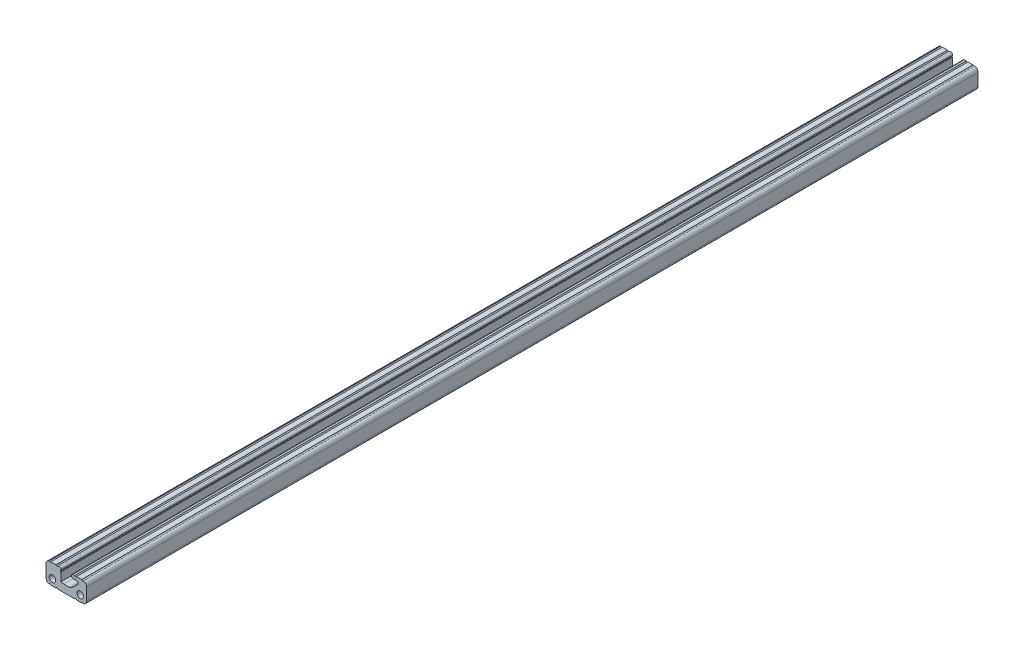
SolidWorks part; units mm, degrees
ref_plane "Front Plane" through (0, 0, 0) normal (0, 0, 1) x (1, 0, 0)
ref_plane "Top Plane" through (0, 0, 0) normal (0, 1, 0) x (1, 0, 0)
ref_plane "Right Plane" through (0, 0, 0) normal (1, 0, 0) x (0, 0, -1)
sketch "Sketch1" plane through (0, 0, 0) normal (0, 0, 1) x (1, 0, 0)
  line L0 (0, 6.35) -> (0, -6.35) construction
  line L1 (0, -6.35) -> (12.7, -6.35)
  line L2 (12.7, -6.35) -> (12.7, 6.35)
  line L3 (12.7, 6.35) -> (3.2512, 6.35)
  line L4 (3.2512, 6.35) -> (3.2512, 4.1402)
  line L5 (3.2512, 4.1402) -> (6.4224, 4.1402)
  line L6 (7.1255, 2.4426) -> (2.9811, -1.7018)
  line L7 (2.9811, -1.7018) -> (0, -1.7018)
  circle A0 centre (8.7249, -2.3876) radius 2.032
  arc A1 (6.4224, 4.1402) -> (7.1255, 2.4426) centre (6.4224, 3.1458) cw
  dimension "Center Hole Diameter" = 4.064
  dimension "D3" = 0.9944
  dimension "Rail Height" = 25.4
  dimension "Rail Width" = 12.7
  dimension "Hole CtoC" = 17.4498
  dimension "D1" = 3.9624
  dimension "T-Slot Width" = 6.5024
  dimension "Thickness" = 2.2098
  dimension "Inner Slot Width" = 14.8336
  dimension "Slot Depth" = 5.842
  dimension "D2" = 45
sketch "Sketch2" plane through (0, 0, 0) normal (1, 0, 0) x (0, 0, -1)
  line L0 (-304.8, -6.35) -> (304.8, -6.35) construction
  line L1 (-279.4, 0) -> (279.4, 0) construction
  dimension "Length" = 609.6
sketch "Sketch3" plane through (0, 0, 0) normal (0, 0, 1) x (1, 0, 0)
  line L0 (3.2512, 6.35) -> (3.2512, 4.1402) construction
  line L1 (12.7, 6.35) -> (3.2512, 6.35) construction
  line L2 (3.2512, 4.1402) -> (6.4224, 4.1402) construction
  line L3 (3.2512, 5.3556) -> (3.2512, 5.1346)
  line L4 (12.7, -6.35) -> (12.7, 6.35) construction
  line L5 (0, -6.35) -> (12.7, -6.35) construction
  line L6 (2.9811, -1.7018) -> (0, -1.7018) construction
  line L7 (7.1255, 2.4426) -> (2.9811, -1.7018) construction
  line L8 (0, -1.7018) -> (1.7454, -1.7018)
  line L9 (4.2456, 4.1402) -> (6.4224, 4.1402)
  line L10 (3.8549, -0.828) -> (7.1255, 2.4426)
  line L11 (0, -1.7018) -> (0, -6.35)
  line L12 (0, -6.35) -> (10.16, -6.35)
  line L13 (12.7, -3.81) -> (12.7, 3.81)
  line L14 (4.2456, 6.35) -> (10.16, 6.35)
  arc A0 (3.2512, 5.3556) -> (4.2456, 6.35) centre (4.2456, 5.3556) cw
  arc A1 (3.2512, 5.1346) -> (4.2456, 4.1402) centre (4.2456, 5.1346) ccw
  arc A2 (7.1255, 2.4426) -> (6.4224, 4.1402) centre (6.4224, 3.1458) ccw construction
  arc A3 (10.16, 6.35) -> (12.7, 3.81) centre (10.16, 3.81) cw
  arc A4 (10.16, -6.35) -> (12.7, -3.81) centre (10.16, -3.81) ccw
  arc A5 (7.1255, 2.4426) -> (6.4224, 4.1402) centre (6.4224, 3.1458) ccw
  circle A6 centre (8.7249, -2.3876) radius 2.032 construction
  circle A7 centre (8.7249, -2.3876) radius 2.032
  arc A8 (1.7454, -1.7018) -> (3.8549, -0.828) centre (1.7454, 1.2814) ccw
  dimension "D2" = 2.9832
extrude "Boss-Extrude1" add sketch "Sketch3" along normal mid plane 609.6
sketch "Sketch4" plane through (0, 0, 0) normal (0, 0, 1) x (1, 0, 0)
  line L0 (12.7, 6.35) -> (3.2512, 6.35) construction
  line L1 (0, -6.35) -> (12.7, -6.35) construction
  line L2 (10.7569, -2.3876) -> (10.7569, 6.35) construction
  line L3 (6.4224, 3.1458) -> (6.4224, 6.35) construction
  circle A0 centre (5.8699, 6.35) radius 0.5524
  circle A1 centre (10.2045, 6.35) radius 0.5524
  circle A2 centre (5.8699, -6.35) radius 0.5524
  circle A3 centre (10.2045, -6.35) radius 0.5524
  circle A4 centre (8.7249, -2.3876) radius 2.032 construction
  dimension "D1" = 1.1049
extrude "Cut-Extrude1" cut sketch "Sketch4" against normal through all both and the other way through all
mirror "Mirror1" about plane through (0, 0, 0) normal (1, 0, 0) of bodies 135
sketch "Sketch5" plane through (0, 0, 304.8) normal (0, 0, 1) x (1, 0, 0)
  line L16 (9.652, 6.35) -> (6.4224, 6.35)
  line L17 (5.3175, 6.35) -> (4.2456, 6.35)
  line L18 (3.2512, 5.3556) -> (3.2512, 5.1346)
  line L19 (4.2456, 4.1402) -> (6.4224, 4.1402)
  line L20 (7.1255, 2.4426) -> (3.8549, -0.828)
  line L21 (1.7454, -1.7018) -> (-1.7454, -1.7018)
  line L22 (-3.8549, -0.828) -> (-7.1255, 2.4426)
  line L23 (-6.4224, 4.1402) -> (-4.2456, 4.1402)
  line L24 (-3.2512, 5.1346) -> (-3.2512, 5.3556)
  line L25 (-4.2456, 6.35) -> (-5.3175, 6.35)
  line L26 (-6.4224, 6.35) -> (-9.652, 6.35)
  line L27 (-12.7, 3.81) -> (-12.7, -3.81)
  line L28 (-9.652, -6.35) -> (-6.4224, -6.35)
  line L29 (-5.3175, -6.35) -> (5.3175, -6.35)
  line L30 (6.4224, -6.35) -> (9.652, -6.35)
  line L31 (12.7, -3.81) -> (12.7, 3.81)
  line L32 (9.652, 6.35) -> (6.4224, 6.35)
  line L33 (5.3175, 6.35) -> (4.2456, 6.35)
  line L34 (3.2512, 5.3556) -> (3.2512, 5.1346)
  line L35 (4.2456, 4.1402) -> (6.4224, 4.1402)
  line L36 (7.1255, 2.4426) -> (3.8549, -0.828)
  line L37 (1.7454, -1.7018) -> (-1.7454, -1.7018)
  line L38 (-3.8549, -0.828) -> (-7.1255, 2.4426)
  line L39 (-6.4224, 4.1402) -> (-4.2456, 4.1402)
  line L40 (-3.2512, 5.1346) -> (-3.2512, 5.3556)
  line L41 (-4.2456, 6.35) -> (-5.3175, 6.35)
  line L42 (-6.4224, 6.35) -> (-9.652, 6.35)
  line L43 (-12.7, 3.81) -> (-12.7, -3.81)
  line L44 (-9.652, -6.35) -> (-6.4224, -6.35)
  line L45 (-5.3175, -6.35) -> (5.3175, -6.35)
  line L46 (6.4224, -6.35) -> (9.652, -6.35)
  line L47 (12.7, -3.81) -> (12.7, 3.81)
  arc A20 (12.7, 3.81) -> (10.7524, 6.2799) centre (10.16, 3.81) ccw
  arc A21 (9.652, 6.35) -> (10.7524, 6.2799) centre (10.2045, 6.35) ccw
  arc A22 (5.3175, 6.35) -> (6.4224, 6.35) centre (5.8699, 6.35) ccw
  arc A23 (4.2456, 6.35) -> (3.2512, 5.3556) centre (4.2456, 5.3556) ccw
  arc A24 (3.2512, 5.1346) -> (4.2456, 4.1402) centre (4.2456, 5.1346) ccw
  arc A25 (7.1255, 2.4426) -> (6.4224, 4.1402) centre (6.4224, 3.1458) ccw
  arc A26 (1.7454, -1.7018) -> (3.8549, -0.828) centre (1.7454, 1.2814) ccw
  arc A27 (-3.8549, -0.828) -> (-1.7454, -1.7018) centre (-1.7454, 1.2814) ccw
  arc A28 (-6.4224, 4.1402) -> (-7.1255, 2.4426) centre (-6.4224, 3.1458) ccw
  arc A29 (-4.2456, 4.1402) -> (-3.2512, 5.1346) centre (-4.2456, 5.1346) ccw
  arc A30 (-3.2512, 5.3556) -> (-4.2456, 6.35) centre (-4.2456, 5.3556) ccw
  arc A31 (-6.4224, 6.35) -> (-5.3175, 6.35) centre (-5.8699, 6.35) ccw
  arc A32 (-10.7524, 6.2799) -> (-9.652, 6.35) centre (-10.2045, 6.35) ccw
  arc A33 (-10.7524, 6.2799) -> (-12.7, 3.81) centre (-10.16, 3.81) ccw
  arc A34 (-12.7, -3.81) -> (-10.7524, -6.2799) centre (-10.16, -3.81) ccw
  arc A35 (-9.652, -6.35) -> (-10.7524, -6.2799) centre (-10.2045, -6.35) ccw
  arc A36 (-5.3175, -6.35) -> (-6.4224, -6.35) centre (-5.8699, -6.35) ccw
  arc A37 (6.4224, -6.35) -> (5.3175, -6.35) centre (5.8699, -6.35) ccw
  arc A38 (10.7524, -6.2799) -> (9.652, -6.35) centre (10.2045, -6.35) ccw
  arc A39 (10.7524, -6.2799) -> (12.7, -3.81) centre (10.16, -3.81) ccw
  arc A40 (12.7, 3.81) -> (10.7524, 6.2799) centre (10.16, 3.81) ccw
  arc A41 (9.652, 6.35) -> (10.7524, 6.2799) centre (10.2045, 6.35) ccw
  arc A42 (5.3175, 6.35) -> (6.4224, 6.35) centre (5.8699, 6.35) ccw
  arc A43 (4.2456, 6.35) -> (3.2512, 5.3556) centre (4.2456, 5.3556) ccw
  arc A44 (3.2512, 5.1346) -> (4.2456, 4.1402) centre (4.2456, 5.1346) ccw
  arc A45 (7.1255, 2.4426) -> (6.4224, 4.1402) centre (6.4224, 3.1458) ccw
  arc A46 (1.7454, -1.7018) -> (3.8549, -0.828) centre (1.7454, 1.2814) ccw
  arc A47 (-3.8549, -0.828) -> (-1.7454, -1.7018) centre (-1.7454, 1.2814) ccw
  arc A48 (-6.4224, 4.1402) -> (-7.1255, 2.4426) centre (-6.4224, 3.1458) ccw
  arc A49 (-4.2456, 4.1402) -> (-3.2512, 5.1346) centre (-4.2456, 5.1346) ccw
  arc A50 (-3.2512, 5.3556) -> (-4.2456, 6.35) centre (-4.2456, 5.3556) ccw
  arc A51 (-6.4224, 6.35) -> (-5.3175, 6.35) centre (-5.8699, 6.35) ccw
  arc A52 (-10.7524, 6.2799) -> (-9.652, 6.35) centre (-10.2045, 6.35) ccw
  arc A53 (-10.7524, 6.2799) -> (-12.7, 3.81) centre (-10.16, 3.81) ccw
  arc A54 (-12.7, -3.81) -> (-10.7524, -6.2799) centre (-10.16, -3.81) ccw
  arc A55 (-9.652, -6.35) -> (-10.7524, -6.2799) centre (-10.2045, -6.35) ccw
  arc A56 (-5.3175, -6.35) -> (-6.4224, -6.35) centre (-5.8699, -6.35) ccw
  arc A57 (6.4224, -6.35) -> (5.3175, -6.35) centre (5.8699, -6.35) ccw
  arc A58 (10.7524, -6.2799) -> (9.652, -6.35) centre (10.2045, -6.35) ccw
  arc A59 (10.7524, -6.2799) -> (12.7, -3.81) centre (10.16, -3.81) ccw
  dimension "D1" = 0
extrude "Cut-Extrude2" cut sketch "Sketch5" against normal offset from surface (50.8 mm away) 558.8 up to face at (0, 1.3921, -304.8)
sketch "Sketch6" plane through (0, 0, -304.8) normal (0, 0, -1) x (-1, 0, 0)
  line L0 (-4.2456, 4.1402) -> (-3.2512, 4.1402) construction
  line L1 (-3.2512, 4.1402) -> (-3.2512, -1.2939) construction
  line L2 (0, 6.985) -> (0, -6.985) construction
  line L3 (6.4224, 4.1402) -> (4.2456, 4.1402)
  line L4 (3.8549, -0.828) -> (7.1255, 2.4426)
  line L5 (3.2512, 4.1402) -> (3.2512, -1.2939)
  line L6 (4.2456, 4.1402) -> (3.2512, 4.1402)
  line L16 (-12.7, 3.81) -> (-12.7, -3.81)
  line L17 (-9.652, -6.35) -> (-6.4224, -6.35)
  line L18 (-5.3175, -6.35) -> (5.3175, -6.35)
  line L19 (6.4224, -6.35) -> (9.652, -6.35)
  line L20 (12.7, -3.81) -> (12.7, 3.81)
  line L21 (9.652, 6.35) -> (6.4224, 6.35)
  line L22 (5.3175, 6.35) -> (4.2456, 6.35)
  line L23 (3.2512, 5.3556) -> (3.2512, 5.1346)
  line L24 (4.2456, 4.1402) -> (6.4224, 4.1402)
  line L25 (7.1255, 2.4426) -> (3.8549, -0.828)
  line L26 (1.7454, -1.7018) -> (-1.7454, -1.7018)
  line L27 (-3.8549, -0.828) -> (-7.1255, 2.4426)
  line L28 (-6.4224, 4.1402) -> (-4.2456, 4.1402)
  line L29 (-3.2512, 5.1346) -> (-3.2512, 5.3556)
  line L30 (-4.2456, 6.35) -> (-5.3175, 6.35)
  line L31 (-6.4224, 6.35) -> (-9.652, 6.35)
  line L43 (-3.8549, -0.828) -> (-7.1255, 2.4426) construction
  line L44 (-6.4224, 4.1402) -> (-4.2456, 4.1402) construction
  arc A0 (6.4224, 4.1402) -> (7.1255, 2.4426) centre (6.4224, 3.1458) cw
  arc A1 (3.8549, -0.828) -> (3.2512, -1.2939) centre (1.7454, 1.2814) cw
  arc A20 (-10.7524, 6.2799) -> (-9.652, 6.35) centre (-10.2045, 6.35) ccw
  arc A21 (-10.7524, 6.2799) -> (-12.7, 3.81) centre (-10.16, 3.81) ccw
  arc A22 (-12.7, -3.81) -> (-10.7524, -6.2799) centre (-10.16, -3.81) ccw
  arc A23 (-9.652, -6.35) -> (-10.7524, -6.2799) centre (-10.2045, -6.35) ccw
  arc A24 (-5.3175, -6.35) -> (-6.4224, -6.35) centre (-5.8699, -6.35) ccw
  arc A25 (6.4224, -6.35) -> (5.3175, -6.35) centre (5.8699, -6.35) ccw
  arc A26 (10.7524, -6.2799) -> (9.652, -6.35) centre (10.2045, -6.35) ccw
  arc A27 (10.7524, -6.2799) -> (12.7, -3.81) centre (10.16, -3.81) ccw
  arc A28 (12.7, 3.81) -> (10.7524, 6.2799) centre (10.16, 3.81) ccw
  arc A29 (9.652, 6.35) -> (10.7524, 6.2799) centre (10.2045, 6.35) ccw
  arc A30 (5.3175, 6.35) -> (6.4224, 6.35) centre (5.8699, 6.35) ccw
  arc A31 (4.2456, 6.35) -> (3.2512, 5.3556) centre (4.2456, 5.3556) ccw
  arc A32 (3.2512, 5.1346) -> (4.2456, 4.1402) centre (4.2456, 5.1346) ccw
  arc A33 (7.1255, 2.4426) -> (6.4224, 4.1402) centre (6.4224, 3.1458) ccw
  arc A34 (1.7454, -1.7018) -> (3.8549, -0.828) centre (1.7454, 1.2814) ccw
  arc A35 (-3.8549, -0.828) -> (-1.7454, -1.7018) centre (-1.7454, 1.2814) ccw
  arc A36 (-6.4224, 4.1402) -> (-7.1255, 2.4426) centre (-6.4224, 3.1458) ccw
  arc A37 (-4.2456, 4.1402) -> (-3.2512, 5.1346) centre (-4.2456, 5.1346) ccw
  arc A38 (-3.2512, 5.3556) -> (-4.2456, 6.35) centre (-4.2456, 5.3556) ccw
  arc A39 (-6.4224, 6.35) -> (-5.3175, 6.35) centre (-5.8699, 6.35) ccw
  arc A55 (-3.8549, -0.828) -> (-3.2512, -1.2939) centre (-1.7454, 1.2814) ccw construction
  arc A56 (-6.4224, 4.1402) -> (-7.1255, 2.4426) centre (-6.4224, 3.1458) ccw construction
  dimension "D1" = 0
extrude "Boss-Extrude2" add sketch "Sketch6" against normal through all
equation "\"D3@Sketch1\"=\"Thickness@Sketch1\"*0.45"
equation "\"D1@Sketch3\"=\"Rail Width@Sketch1\"*0.2"
equation "\"D2@Sketch3\"=\"D3@Sketch1\"*3"
equation "\"D1@Boss-Extrude1\"=\"length@sketch2\""
equation "\"D1@Sketch4\"=\"Thickness@Sketch1\"*0.5"
